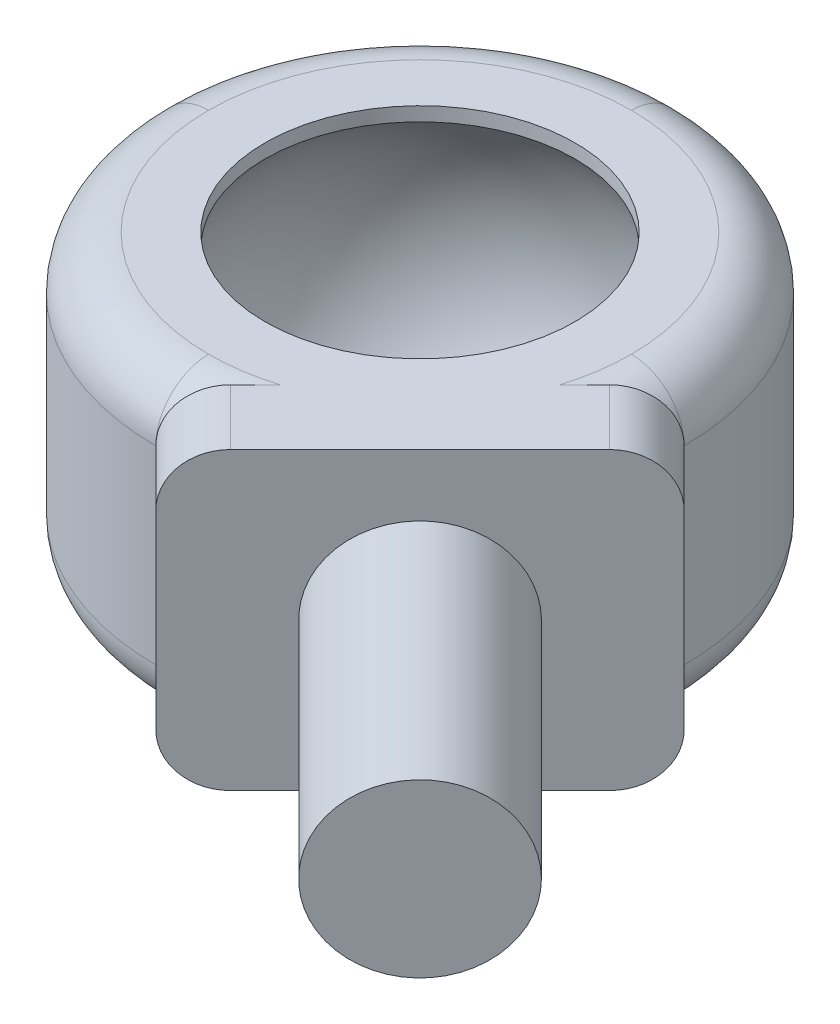
SolidWorks part; units mm, degrees
ref_plane "Front Plane" through (0, 0, 0) normal (0, 0, 1) x (1, 0, 0)
ref_plane "Top Plane" through (0, 0, 0) normal (0, 1, 0) x (1, 0, 0)
ref_plane "Right Plane" through (0, 0, 0) normal (1, 0, 0) x (0, 0, -1)
sketch "Sketch1" plane through (0, 0, 0) normal (0, 1, 0) x (1, 0, 0)
  line L1 (0, 0) -> (-20, 0)
  line L2 (0, 0) -> (0, 20)
  line L3 (0, 20) -> (-20, 20)
  line L4 (-20, 0) -> (-20, 20)
  dimension "D1" = 20
  dimension "D2" = 20
extrude "Boss-Extrude1" add sketch "Sketch1" along normal blind 11.18
sketch3d "3DSketch1"
  point P0 (-10.0851, 5.7357, 0)
sketch3d "3DSketch2"
  point P0 (-11.7076, 7.6552, 0)
ref_plane "Plane3" through (0, 0, -10) normal (0, 0, 1) x (1, 0, 0)
sketch "Sketch2" plane through (0, 0, -10) normal (0, 0, 1) x (1, 0, 0)
  line L0 (-20, 11.18) -> (0, 11.18) construction
  line L1 (-10, 13.34) -> (-10, -2.16)
  line L2 (-20, 11.18) -> (-20, 0) construction
  arc A0 (-10, 13.34) -> (-10, -2.16) centre (-10, 5.59) ccw
  dimension "D1" = 15.5
  dimension "D2" = 5.59
  dimension "D3" = 10
revolve "Cut-Revolve1" cut sketch "Sketch2" angle 360 about L1
fillet "Fillet1" radius 10 4 edges at (-20, 5.59, 0) (-20, 5.59, -20) (0, 5.59, -20) (0, 5.59, 0)
fillet "Fillet2" radius 2 8 edges at (-17.0711, 0, -2.9289) (-2.9289, 0, -2.9289) (-2.9289, 0, -17.0711) (-2.9289, 11.18, -17.0711) (-2.9289, 11.18, -2.9289) (-17.0711, 11.18, -2.9289) (-17.0711, 0, -17.0711) (-17.0711, 11.18, -17.0711)
ref_plane "Plane5" through (-5, 0, -5) normal (0.7071, 0, 0.7071) x (0.7071, 0, -0.7071)
sketch "Sketch4" plane through (-5, 0, -5) normal (0.7071, 0, 0.7071) x (0.7071, 0, -0.7071)
  line L0 (7.0711, 2) -> (7.0711, 9.18) construction
  line L1 (-5.0711, 11.18) -> (5.0711, 11.18)
  line L2 (-7.0711, 9.18) -> (-7.0711, 2)
  line L3 (-5.0711, 0) -> (5.0711, 0)
  line L4 (7.0711, 9.18) -> (7.0711, 2)
  line L5 (-7.0711, 2) -> (-7.0711, 9.18) construction
  line L6 (5.6569, 11.18) -> (-5.6569, 11.18) construction
  line L7 (-5.6569, 0) -> (5.6569, 0) construction
  arc A0 (-7.0711, 2) -> (-5.0711, 0) centre (-5.0711, 2) ccw
  arc A1 (5.0711, 0) -> (7.0711, 2) centre (5.0711, 2) ccw
  arc A2 (5.0711, 11.18) -> (7.0711, 9.18) centre (5.0711, 9.18) cw
  arc A3 (-5.0711, 11.18) -> (-7.0711, 9.18) centre (-5.0711, 9.18) ccw
  dimension "D1" = 2
extrude "Boss-Extrude2" add sketch "Sketch4" along normal blind 15
sketch "Sketch5" plane through (5.6066, 0, 5.6066) normal (0.7071, 0, 0.7071) x (0.7071, 0, -0.7071)
  line L1 (7.0711, 2) -> (7.0711, 9.18) construction
  line L2 (5.0711, 11.18) -> (-5.0711, 11.18) construction
  circle A0 centre (0, 5.59) radius 3.25
  point P2 (0, 0)
  point P3 (0, 5.3077)
  dimension "D1" = 6.5
  dimension "D2" = 5.59
  dimension "D3" = 7.0711
extrude "Cut-Extrude1" cut sketch "Sketch5" against normal blind 12 flip side to cut
chamfer "Chamfer1" distance 0.5 angle 90 1 edges at (-10, 11.18, -4.6321) first distance on face at (-10, 11.18, -4.6321)
chamfer "Chamfer2" distance 0.5 angle 45 1 edges at (-10, 0, -4.6321) first distance on face at (-10, 10.6526, -15.8679)
sketch "Sketch6" [suppressed] plane through (5.6066, 0, 5.6066) normal (0.7071, 0, 0.7071) x (0.7071, 0, -0.7071)
  line L0 (-5.0711, 0) -> (5.0711, 0) construction
  line L4 (7.0711, 2) -> (7.0711, 9.18) construction
  circle A0 centre (0, 5.59) radius 3.1
  dimension "D1" = 6.2
  dimension "D3" = 7.0711
  dimension "D2" = 5.59
extrude "Cut-Extrude2" [suppressed] cut sketch "Sketch6" against normal blind 12
